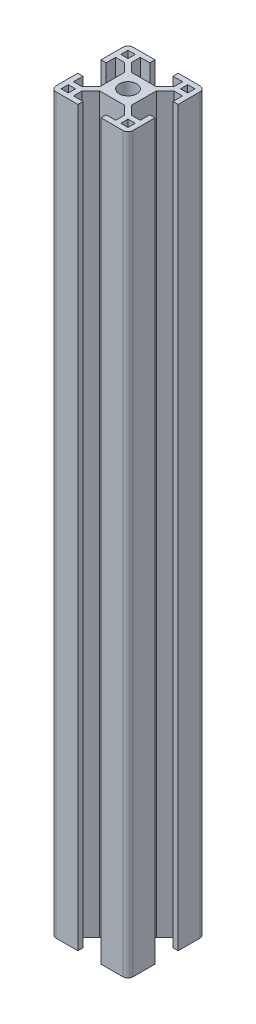
SolidWorks part; units mm, degrees
ref_plane "Front plane" through (0, 0, 0) normal (0, 0, 1) x (1, 0, 0)
ref_plane "Top plane" through (0, 0, 0) normal (0, 1, 0) x (1, 0, 0)
ref_plane "Right plane" through (0, 0, 0) normal (1, 0, 0) x (0, 0, -1)
ref_axis "Axis X" through (0, 0, 0) along (1, 0, 0)
ref_axis "Axis Y" through (0, 0, 0) along (0, 1, 0)
ref_axis "Axis Z" through (0, 0, 0) along (0, 0, 1)
sketch "Sketch1" plane through (0, 0, 0) normal (0, 1, 0) x (1, 0, 0)
  line L1 (-10, 10) -> (10, 10)
  line L2 (-10, 10) -> (-10, -10)
  line L3 (-10, -10) -> (10, -10)
  line L4 (10, 10) -> (10, -10)
  line L5 (-10, 10) -> (10, -10) construction
  line L6 (-10, -10) -> (10, 10) construction
  point P0 (0, 0)
  dimension "D1" = 20
  dimension "D2" = 20
extrude "Extrude1" add sketch "Sketch1" along normal blind 190
sketch "Sketch2" plane through (0, 190, 0) normal (0, 1, 0) x (1, 0, 0)
  line L0 (0, 0) -> (10, 0) construction
  line L1 (10, -10) -> (10, 10) construction
  line L2 (10, 10) -> (-10, 10) construction
  line L3 (8.6667, 3) -> (11.3333, 3)
  line L4 (8.6667, 3) -> (8.6667, -3) construction
  line L5 (8.6667, -3) -> (11.3333, -3)
  line L6 (11.3333, 3) -> (11.3333, -3)
  line L7 (8.6667, 3) -> (11.3333, -3) construction
  line L8 (8.6667, -3) -> (11.3333, 3) construction
  line L9 (6.8, 8.6667) -> (8.6667, 8.6667)
  line L10 (6.8, 8.6667) -> (6.8, 6.8)
  line L11 (6.8, 6.8) -> (8.6667, 6.8)
  line L12 (8.6667, 8.6667) -> (8.6667, 6.8)
  line L13 (6.8, 8.6667) -> (8.6667, 6.8) construction
  line L14 (6.8, 6.8) -> (8.6667, 8.6667) construction
  line L15 (0, 0) -> (10, 10) construction
  line L16 (8.6667, 3) -> (8.6667, 5.4667)
  line L17 (8.6667, 5.4667) -> (6.4095, 5.4667)
  line L18 (6.4095, 5.4667) -> (4.1333, 3.1905)
  line L19 (4.1333, 3.1905) -> (4.1333, -3.1905)
  line L20 (4.1333, -3.1905) -> (6.4095, -5.4667)
  line L21 (6.4095, -5.4667) -> (8.6667, -5.4667)
  line L22 (8.6667, -5.4667) -> (8.6667, -3)
  line L65 (-3.1905, 4.1333) -> (-5.4667, 6.4095)
  line L66 (-5.4667, 6.4095) -> (-5.4667, 8.6667)
  line L67 (-5.4667, 8.6667) -> (-3, 8.6667)
  line L68 (3, 11.3333) -> (-3, 11.3333)
  line L69 (-3, 8.6667) -> (-3, 11.3333)
  line L70 (3, 8.6667) -> (3, 11.3333)
  line L71 (3, 8.6667) -> (5.4667, 8.6667)
  line L72 (5.4667, 8.6667) -> (5.4667, 6.4095)
  line L73 (5.4667, 6.4095) -> (3.1905, 4.1333)
  line L74 (3.1905, 4.1333) -> (-3.1905, 4.1333)
  line L75 (0, 10) -> (0, -10) construction
  line L76 (-10, -10) -> (10, -10) construction
  line L77 (0, 0) -> (-10, 0) construction
  line L78 (-10, 10) -> (-10, -10) construction
  line L79 (8.6667, -8.6667) -> (8.6667, -6.8)
  line L80 (6.8, -6.8) -> (8.6667, -6.8)
  line L81 (6.8, -8.6667) -> (6.8, -6.8)
  line L82 (6.8, -8.6667) -> (8.6667, -8.6667)
  line L83 (-6.8, 6.8) -> (-8.6667, 6.8)
  line L84 (-8.6667, 8.6667) -> (-8.6667, 6.8)
  line L85 (-6.8, 8.6667) -> (-8.6667, 8.6667)
  line L86 (-6.8, 8.6667) -> (-6.8, 6.8)
  line L87 (-6.8, -8.6667) -> (-8.6667, -8.6667)
  line L88 (-6.8, -8.6667) -> (-6.8, -6.8)
  line L89 (-6.8, -6.8) -> (-8.6667, -6.8)
  line L90 (-8.6667, -8.6667) -> (-8.6667, -6.8)
  line L91 (-6.4095, -5.4667) -> (-8.6667, -5.4667)
  line L92 (-4.1333, -3.1905) -> (-6.4095, -5.4667)
  line L93 (-4.1333, 3.1905) -> (-4.1333, -3.1905)
  line L94 (-6.4095, 5.4667) -> (-4.1333, 3.1905)
  line L95 (-8.6667, 5.4667) -> (-6.4095, 5.4667)
  line L96 (-8.6667, 3) -> (-8.6667, 5.4667)
  line L97 (-8.6667, 3) -> (-11.3333, 3)
  line L98 (-11.3333, 3) -> (-11.3333, -3)
  line L99 (-8.6667, -3) -> (-11.3333, -3)
  line L100 (-8.6667, -5.4667) -> (-8.6667, -3)
  line L101 (3.1905, -4.1333) -> (-3.1905, -4.1333)
  line L102 (5.4667, -6.4095) -> (3.1905, -4.1333)
  line L103 (5.4667, -8.6667) -> (5.4667, -6.4095)
  line L104 (3, -8.6667) -> (5.4667, -8.6667)
  line L105 (3, -8.6667) -> (3, -11.3333)
  line L106 (3, -11.3333) -> (-3, -11.3333)
  line L107 (-3, -8.6667) -> (-3, -11.3333)
  line L108 (-5.4667, -8.6667) -> (-3, -8.6667)
  line L109 (-5.4667, -6.4095) -> (-5.4667, -8.6667)
  line L110 (-3.1905, -4.1333) -> (-5.4667, -6.4095)
  circle A0 centre (0, 0) radius 2.2667
  point P9 (7.7333, 7.7333)
  point P20 (7.5381, 5.4667)
  point P27 (10, -3)
  point P34 (-3, 10)
  point P37 (5.4667, 7.5381)
  dimension "D10" = 4.5333
  dimension "D1" = 2.6667
  dimension "D2" = 6
  dimension "D3" = 1.3333
  dimension "D4" = 1.3333
  dimension "D5" = 4.5333
  dimension "D6" = 5.4667
  dimension "D7" = 0.6667
  dimension "D8" = 1.3333
extrude "Extrude2" cut sketch "Sketch2" against normal through all
fillet "Fillet1" radius 1.3333 4 edges at (10, 95, 10) (10, 95, -10) (-10, 95, 10) (-10, 95, -10)
sketch "Эскиз1" plane through (10, 0, 0) normal (1, 0, 0) x (0, 0, -1)
  line L0 (0, 0) -> (0, 190) construction
  line L1 (3.1905, 190) -> (-3.1905, 190) construction
  line L2 (0, 100) -> (-56.213, 100) construction
  line L3 (-8.6667, 0) -> (-3, 0) construction
  circle A0 centre (0, 93) radius 2.5
  circle A1 centre (0, 107) radius 2.5
  dimension "D1" = 5
  dimension "D2" = 14
  dimension "D3" = 100
extrude "Вырез-Вытянуть1" cut sketch "Эскиз1" against normal through all
equation "\"prof_width\"= 20'Aluminium profile parameters"
equation "\"D1@Sketch1\"=\"prof_width\""
equation "\"D2@Sketch1\"=\"prof_width\""
equation "\"prof_groove\"= 6"
equation "\"prof_length\" = 190"
equation "\"D1@Extrude1\"=\"prof_length\""
equation "\"D1@Sketch2\"=\"prof_width\"/30*4"
equation "\"D2@Sketch2\"=\"prof_groove\""
equation "\"D3@Sketch2\"=\"D1@Sketch2\"/2"
equation "\"D4@Sketch2\"=\"D3@Sketch2\""
equation "\"D5@Sketch2\"=\"prof_width\"/30*6.8"
equation "\"D6@Sketch2\"=\"prof_width\"/30*8.2"
equation "\"D7@Sketch2\"=\"D3@Sketch2\"/2"
equation "\"D8@Sketch2\"=\"D3@Sketch2\""
equation "\"D10@Sketch2\"=\"prof_width\"/30*6.8"
equation "\"D1@Fillet1\"=\"prof_width\"/30*2"
